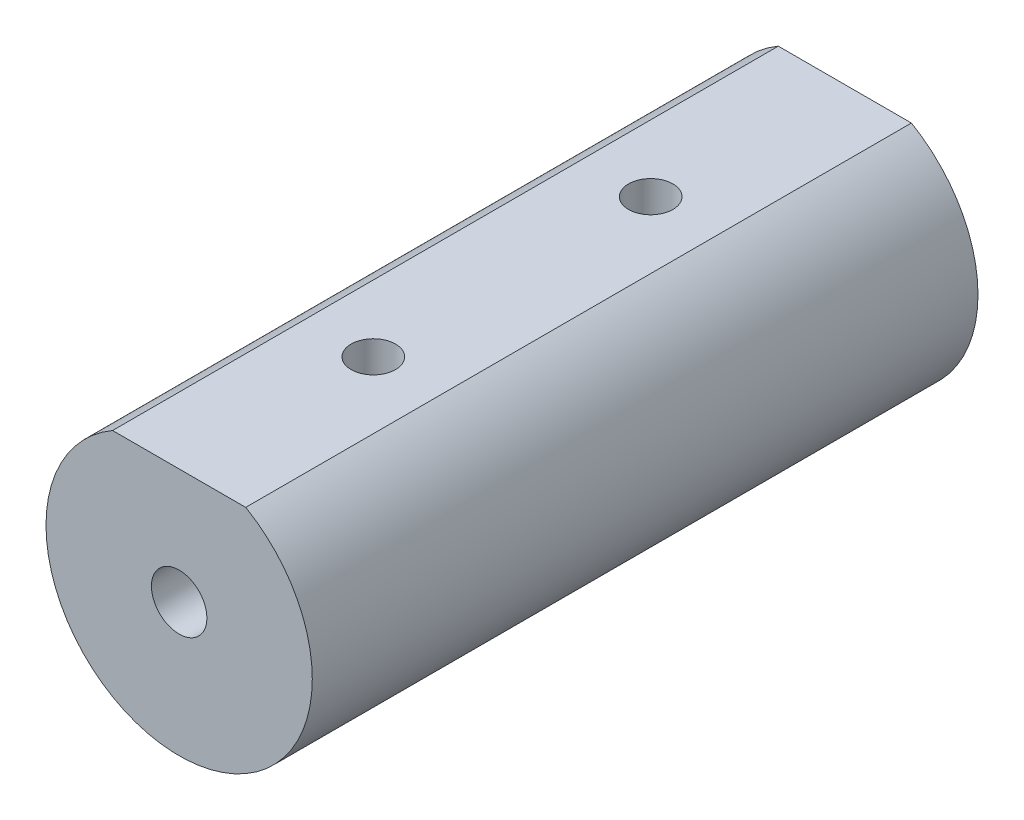
SolidWorks part; units mm, degrees
ref_plane "Front Plane" through (0, 0, 0) normal (0, 0, 1) x (1, 0, 0)
ref_plane "Top Plane" through (0, 0, 0) normal (0, 1, 0) x (1, 0, 0)
ref_plane "Right Plane" through (0, 0, 0) normal (1, 0, 0) x (0, 0, -1)
sketch "Sketch1" plane through (0, 0, 0) normal (1, 0, 0) x (0, 0, -1)
  line L0 (0, 2.5) -> (60, 2.5)
  line L1 (60, 2.5) -> (60, 12)
  line L2 (60, 12) -> (0, 12)
  line L3 (0, 12) -> (0, 2.5)
  line L4 (0, 0) -> (60, 0) construction
  dimension "D1" = 2.5
  dimension "D2" = 60
  dimension "D3" = 12
revolve "Revolve1" add sketch "Sketch1" angle 360 about L4
sketch "Sketch2" plane through (0, 0, -60) normal (0, 0, -1) x (-1, 0, 0)
  line L1 (6, 10.3923) -> (-6, 10.3923)
  circle A0 centre (0, 0) radius 12 construction
  arc A1 (-6, 10.3923) -> (6, 10.3923) centre (0, 0) cw
  dimension "D1" = 12
extrude "Cut-Extrude1" cut sketch "Sketch2" against normal up to next
sketch "Sketch3" plane through (0, 10.3923, 0) normal (0, 1, 0) x (1, 0, 0)
  line L0 (0, 0) -> (0, 60) construction
  line L1 (-6, 0) -> (6, 0) construction
  line L2 (6, 60) -> (-6, 60) construction
  line L3 (6, 30) -> (-6, 30) construction
  line L4 (6, 0) -> (6, 60) construction
  line L5 (-6, 0) -> (-6, 60) construction
  circle A0 centre (0, 42.5) radius 2
  circle A1 centre (0, 17.5) radius 2
  dimension "D2" = 4
  dimension "D1" = 25
extrude "Cut-Extrude2" cut sketch "Sketch3" against normal up to next
